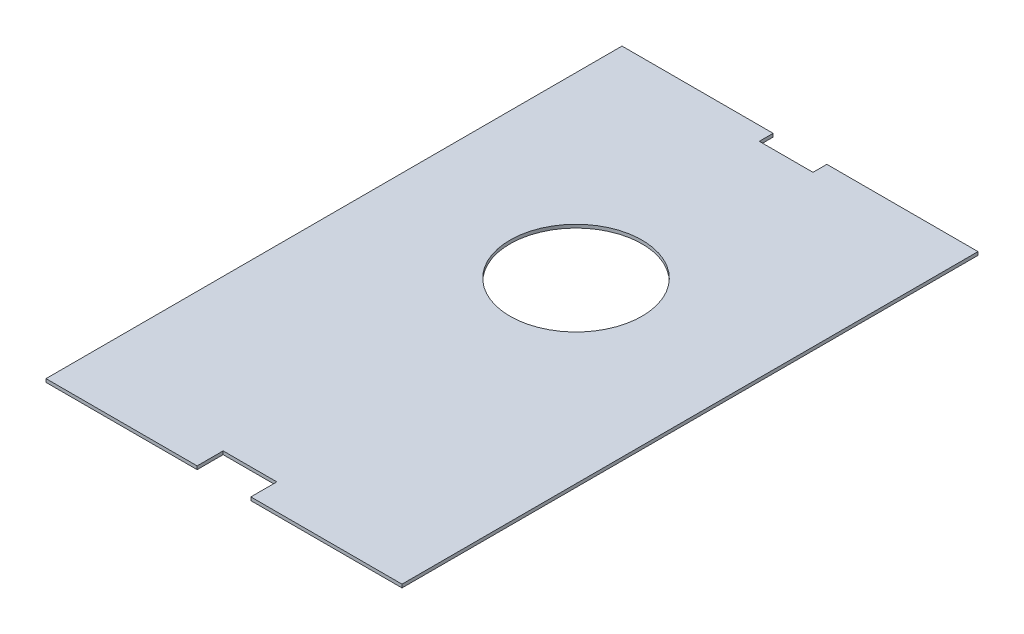
SolidWorks part; units mm, degrees
ref_plane "Front Plane" through (0, 0, 0) normal (0, 0, 1) x (1, 0, 0)
ref_plane "Top Plane" through (0, 0, 0) normal (0, 1, 0) x (1, 0, 0)
ref_plane "Right Plane" through (0, 0, 0) normal (1, 0, 0) x (0, 0, -1)
sketch "BaseSketch" plane through (0, 0, 0) normal (0, 1, 0) x (1, 0, 0)
  line L0 (0, -2.0955) -> (0, 2.0955) construction
  line L1 (-190.5, -317.5) -> (190.5, -317.5)
  line L2 (-190.5, -317.5) -> (-190.5, 317.5)
  line L3 (-190.5, 317.5) -> (190.5, 317.5)
  line L4 (190.5, -317.5) -> (190.5, 317.5)
  line L5 (-190.5, -317.5) -> (190.5, 317.5) construction
  line L6 (-190.5, 317.5) -> (190.5, -317.5) construction
  point P0 (0, 0)
  dimension "D1" = 90
extrude "Boss-Extrude1" add sketch "BaseSketch" along normal blind 3.81
sketch "Sketch7" plane through (0, 3.81, 0) normal (0, 1, 0) x (1, 0, 0)
  line L8 (205.5, -332.5) -> (205.5, 332.5)
  line L9 (205.5, 332.5) -> (-205.5, 332.5)
  line L10 (-205.5, 332.5) -> (-205.5, -332.5)
  line L11 (-205.5, -332.5) -> (205.5, -332.5)
  line L12 (205.5, -332.5) -> (205.5, 332.5)
  line L13 (205.5, 332.5) -> (-205.5, 332.5)
  line L14 (-205.5, 332.5) -> (-205.5, -332.5)
  line L15 (-205.5, -332.5) -> (205.5, -332.5)
  dimension "D1" = 15
extrude "Boss-Extrude2" add sketch "Sketch7" against normal up to surface (3.81 mm away) up to face at (0, 0, 0)
sketch "TabCutSketch" plane through (0, 3.81, 0) normal (0, 1, 0) x (1, 0, 0)
  line L1 (-31, -332.5) -> (31, -332.5)
  line L2 (-31, -332.5) -> (-31, -302.5)
  line L3 (-31, -302.5) -> (31, -302.5)
  line L4 (31, -332.5) -> (31, -302.5)
  line L5 (-205.5, -332.5) -> (205.5, -332.5) construction
  line L10 (0, 0) -> (0, 316.5) construction
  line L11 (0, 316.5) -> (0, 0) construction
  line L13 (31, 332.5) -> (-31, 332.5)
  line L14 (31, 332.5) -> (31, 316.5)
  line L15 (31, 316.5) -> (-31, 316.5)
  line L16 (-31, 332.5) -> (-31, 316.5)
  line L17 (0, 0) -> (0, -302.5) construction
  line L18 (205.5, 332.5) -> (-205.5, 332.5) construction
  point P0 (0, -332.5)
  dimension "D1" = 30
  dimension "D2" = 62
  dimension "D3" = 16
  dimension "D4" = 62
extrude "Cut-Extrude1" cut sketch "TabCutSketch" against normal through all
sketch "Sketch6" plane through (0, 3.81, 0) normal (0, 1, 0) x (1, 0, 0)
  line L0 (0, 73.9) -> (0, 316.5) construction
  line L1 (31, -332.5) -> (205.5, -332.5) construction
  line L2 (-31, 316.5) -> (31, 316.5) construction
  circle A0 centre (0, 73.9) radius 76.2
  dimension "D2" = 152.4
  dimension "D1" = 406.4
extrude "Cut-Extrude10" cut sketch "Sketch6" against normal blind 3.81
